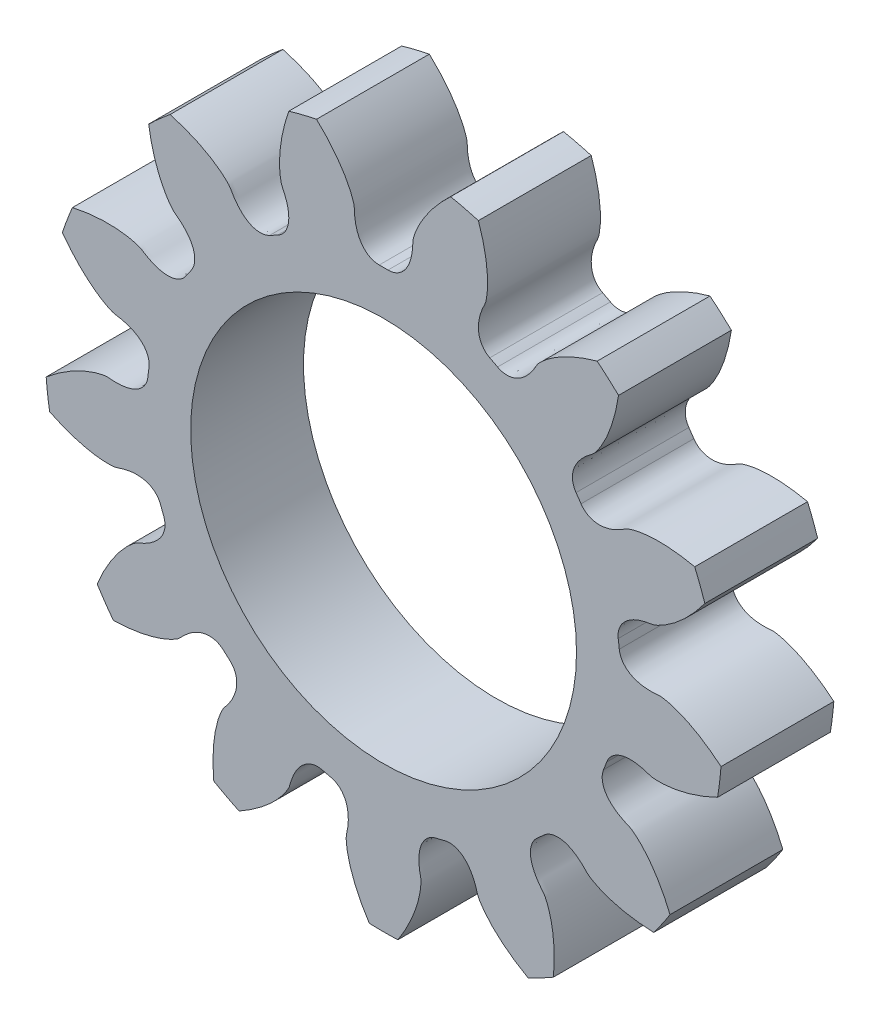
SolidWorks part; units mm, degrees
ref_plane "Front Plane" through (0, 0, 0) normal (0, 0, 1) x (1, 0, 0)
ref_plane "Top Plane" through (0, 0, 0) normal (0, 1, 0) x (1, 0, 0)
ref_plane "Right Plane" through (0, 0, 0) normal (1, 0, 0) x (0, 0, -1)
ref_axis "Axis1" through (0, 0, -88.99) along (0, 0, 1)
sketch "Gear-BaseSketch" plane through (0, 0, 0) normal (0, 0, 1) x (1, 0, 0)
  circle A0 centre (0, 0) radius 19.05
  dimension "D1" = 38.1
extrude "Non-standard pitches, 1.3000in P.D." add sketch "Gear-BaseSketch" along normal mid plane 6.35
sketch "Tooth-Sketch; Backlash: 0.0000in" plane through (0, 0, 0) normal (0, 0, 1) x (1, 0, 0)
  line L0 (0, 0) -> (0, 23.2715) construction
  arc A0 (-3.8481, 18.7422) -> (3.8481, 18.7422) centre (0, 0) cw
  arc A1 (-0.2469, 13.3327) -> (0.2469, 13.3327) centre (0, 0) cw
  spline S0 degree 3 poles (-3.8481, 18.7422) (-3.7218, 18.6231) (-3.478, 18.393) (-3.1459, 18.0393) (-2.8536, 17.6984) (-2.6002, 17.372) (-2.3833, 17.0633) (-2.2008, 16.7749) (-2.05, 16.5093) (-1.9283, 16.2688) (-1.8331, 16.0556) (-1.7608, 15.8716) (-1.71, 15.7183) (-1.6299, 15.4535) (-1.6449, 15.1831) (-1.6133, 14.9199) (-1.5946, 14.7948) (-1.5639, 14.635) (-1.5147, 14.4435) (-1.4363, 14.2255) (-1.3369, 14.0209) (-1.2124, 13.8297) (-1.0567, 13.654) (-0.862, 13.5004) (-0.6238, 13.3833) (-0.4097, 13.3382) (-0.2814, 13.3339) (-0.2469, 13.3327) knots 0 0 0 0 0.076117 0.146985 0.212603 0.272972 0.328091 0.377961 0.422581 0.461952 0.496073 0.524945 0.548568 0.566941 0.645853 0.664795 0.683262 0.701286 0.736155 0.769796 0.802733 0.835673 0.869515 0.905271 0.943737 0.984874 1 1 1 1
  spline S1 degree 3 poles (3.8481, 18.7422) (3.7218, 18.6231) (3.478, 18.393) (3.1459, 18.0393) (2.8536, 17.6984) (2.6002, 17.372) (2.3833, 17.0633) (2.2008, 16.7749) (2.05, 16.5093) (1.9283, 16.2688) (1.8331, 16.0556) (1.7608, 15.8716) (1.71, 15.7183) (1.6299, 15.4535) (1.6449, 15.1831) (1.6133, 14.9199) (1.5946, 14.7948) (1.5639, 14.635) (1.5147, 14.4435) (1.4363, 14.2255) (1.3369, 14.0209) (1.2124, 13.8297) (1.0567, 13.654) (0.862, 13.5004) (0.6238, 13.3833) (0.4097, 13.3382) (0.2814, 13.3339) (0.2469, 13.3327) knots 0 0 0 0 0.076117 0.146985 0.212603 0.272972 0.328091 0.377961 0.422581 0.461952 0.496073 0.524945 0.548568 0.566941 0.645853 0.664795 0.683262 0.701286 0.736155 0.769796 0.802733 0.835673 0.869515 0.905271 0.943737 0.984874 1 1 1 1
extrude "Tooth-Cut, D.P.=10.0000, P.A.=20.000deg" cut sketch "Tooth-Sketch; Backlash: 0.0000in" against normal through all and the other way through all
pattern_circular "Tooth Pattern, 13 / 13" count 13 over 360 about axis through (0, 0, -88.99) along (0, 0, 1) of "Tooth-Cut, D.P.=10.0000, P.A.=20.000deg"
sketch "Sketch1" plane through (0, 0, 3.175) normal (0, 0, 1) x (1, 0, 0)
  circle A0 centre (0, 0) radius 10.8585
  dimension "D1" = 21.717
extrude "Extrude1" cut sketch "Sketch1" against normal through all
